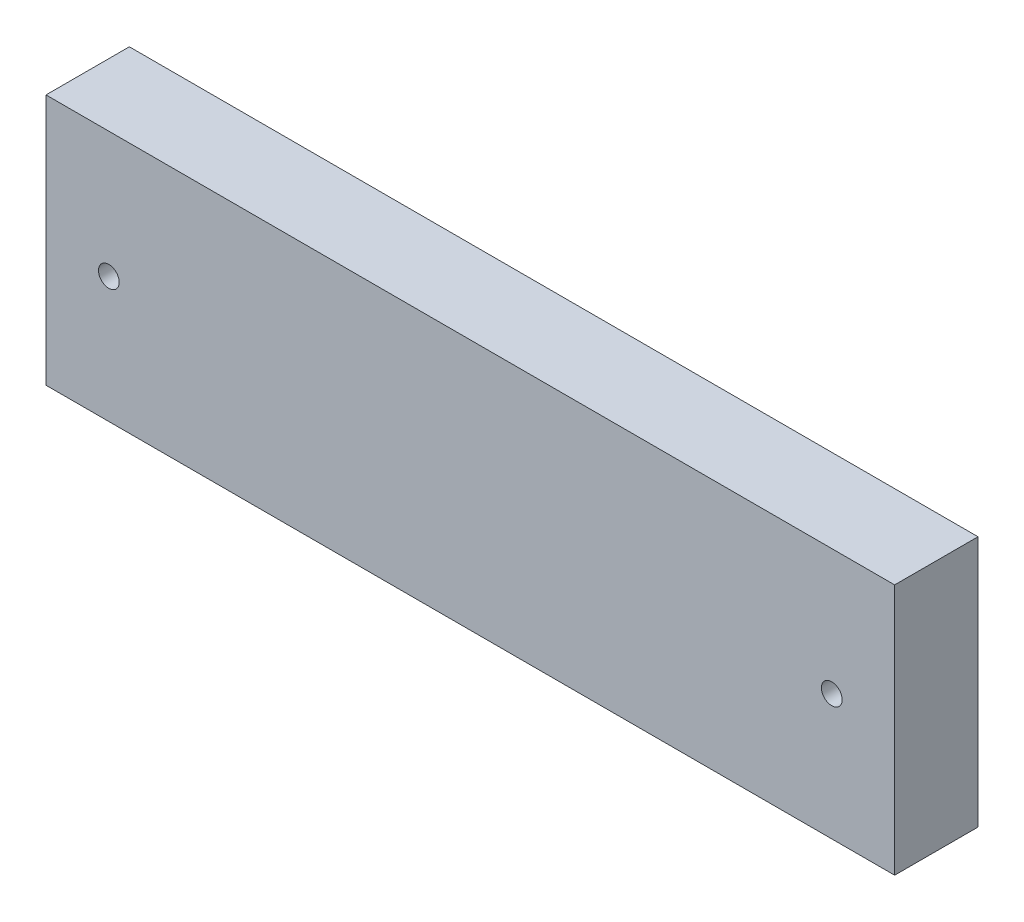
SolidWorks part; units mm, degrees
material "1060 Alloy"
ref_plane "Front Plane" through (0, 0, 0) normal (0, 0, 1) x (1, 0, 0)
ref_plane "Top Plane" through (0, 0, 0) normal (0, 1, 0) x (1, 0, 0)
ref_plane "Right Plane" through (0, 0, 0) normal (1, 0, 0) x (0, 0, -1)
sketch "Sketch1" plane through (0, 0, 0) normal (0, 0, 1) x (1, 0, 0)
  line L1 (-67.5, 20) -> (67.5, 20)
  line L2 (-67.5, 20) -> (-67.5, -20)
  line L3 (-67.5, -20) -> (67.5, -20)
  line L4 (67.5, 20) -> (67.5, -20)
  line L5 (-67.5, 20) -> (67.5, -20) construction
  line L6 (-67.5, -20) -> (67.5, 20) construction
  point P0 (0, 0)
  dimension "D1" = 40
  dimension "D2" = 135
extrude "Boss-Extrude1" add sketch "Sketch1" along normal mid plane 13.26
hole_wizard "M4x0.7 Tapped Hole1" positions "Sketch3" profile "Sketch2" tap size "M4x0.7" standard "ANSI Metric" end condition through all
sketch "Sketch3" plane through (0, 0, 6.63) normal (0, 0, 1) x (1, 0, 0)
  line L0 (-67.5, 20) -> (-67.5, -20) construction
  line L2 (67.5, -20) -> (67.5, 20) construction
  line L3 (67.5, 20) -> (-67.5, 20) construction
  point P0 (57.5, 0)
  point P2 (-57.5, 0)
  point P11 (67.5, 0)
  dimension "D1" = 10
  dimension "D2" = 10
  dimension "D3" = 20
sketch "Sketch2" plane through (57.5, 0, 6.63) normal (1, 0, 0) x (0, -1, 0)
  line L0 (0, 0) -> (0, 13.26)
  line L1 (0, 13.26) -> (1.65, 13.26)
  line L2 (1.65, 13.26) -> (1.65, 0)
  line L5 (1.65, 0) -> (0, 0)
  line L11 (0, -6.35) -> (0, 107.95) construction
  dimension "Thru Tap Drill Dia." = 3.3
  dimension "Thru Tap Drill Depth" = 13.26
cosmetic thread "Hole Thread1" parameters "D2"=4
cosmetic thread "Hole Thread2" parameters "D2"=4
ref_axis "Axis1" through (-57.5, 0, -6.63) along (0, 0, 1)
